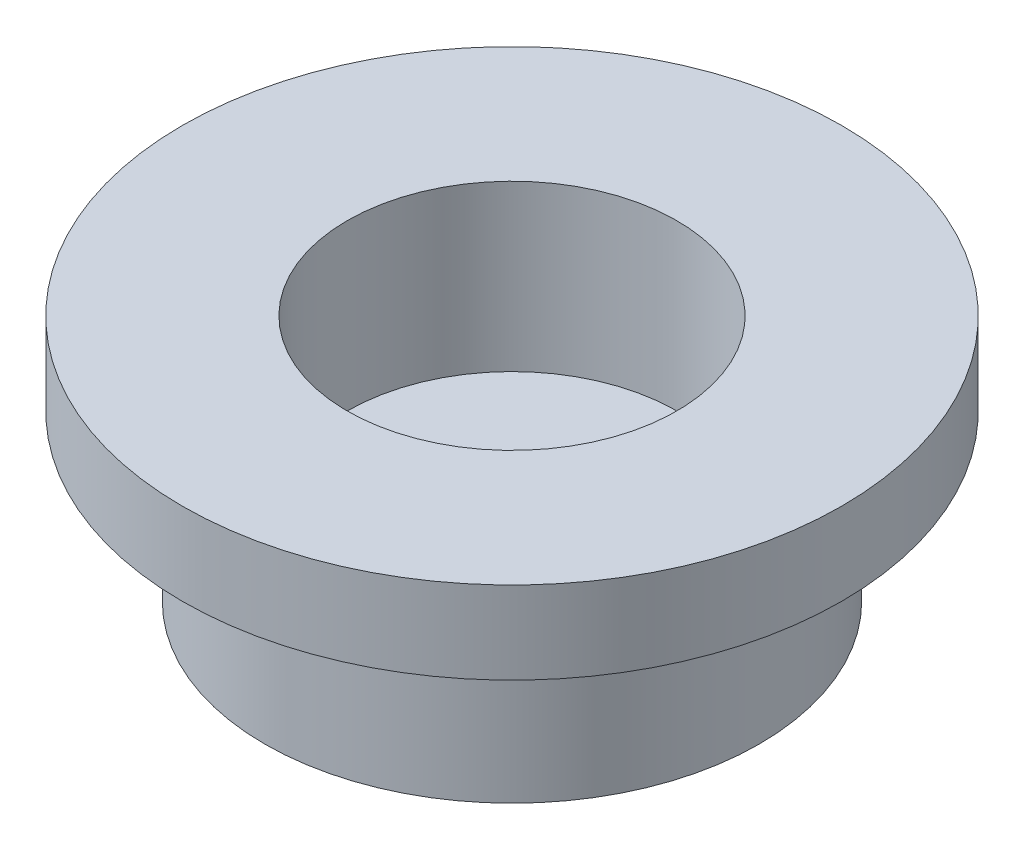
SolidWorks part; units mm, degrees
material "ABS"
ref_plane "Front Plane" through (0, 0, 0) normal (0, 0, 1) x (1, 0, 0)
ref_plane "Top Plane" through (0, 0, 0) normal (0, 1, 0) x (1, 0, 0)
ref_plane "Right Plane" through (0, 0, 0) normal (1, 0, 0) x (0, 0, -1)
sketch "Sketch1" plane through (0, 0, 0) normal (0, 0, 1) x (1, 0, 0)
  line L0 (0, 0) -> (0, -6) construction
  line L1 (0, -6) -> (6, -6)
  line L2 (6, -6) -> (6, -2)
  line L3 (6, -2) -> (8, -2)
  line L4 (8, -2) -> (8, 0)
  line L5 (8, 0) -> (4, 0)
  line L6 (4, 0) -> (4, -4)
  line L7 (4, -4) -> (0, -4)
  line L8 (0, -4) -> (0, -6)
  dimension "D1" = 2
  dimension "D2" = 2
  dimension "D3" = 4
  dimension "D4" = 6
  dimension "D5" = 6
  dimension "D6" = 8
revolve "Revolve1" add sketch "Sketch1" angle 360 about L0
